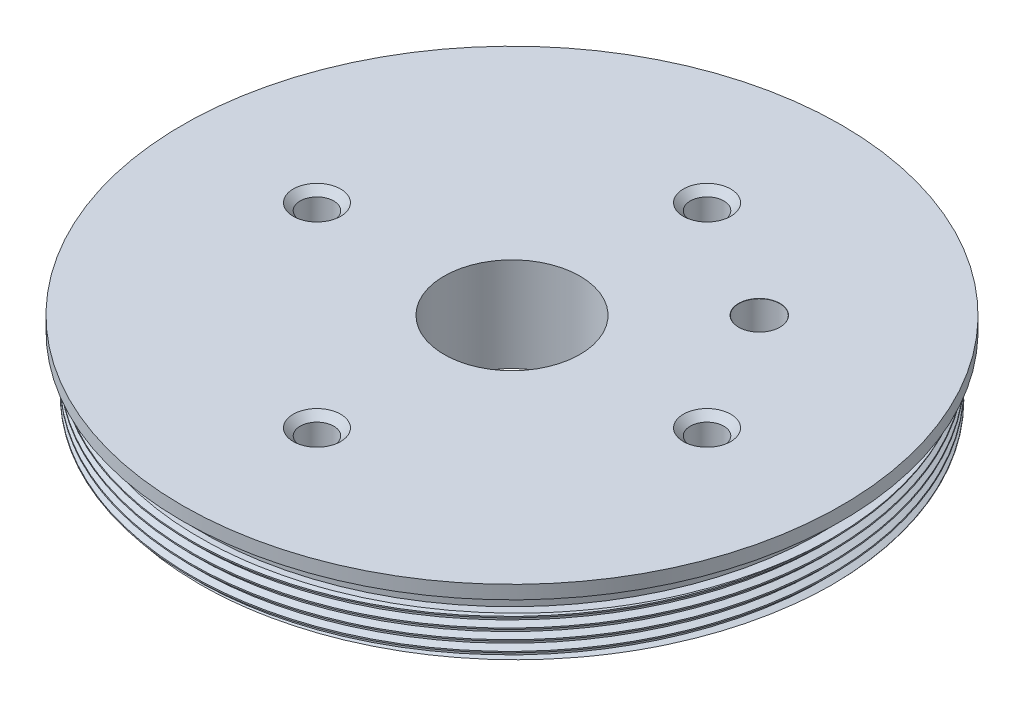
SolidWorks part; units mm, degrees
material "1.4305 (X8CrNiS18-9)"
ref_plane "Ebene vorne" through (0, 0, 0) normal (0, 0, 1) x (1, 0, 0)
ref_plane "Ebene oben" through (0, 0, 0) normal (0, 1, 0) x (1, 0, 0)
ref_plane "Ebene rechts" through (0, 0, 0) normal (1, 0, 0) x (0, 0, -1)
sketch "Sketch1" plane through (0, 0, 0) normal (0, 0, 1) x (1, 0, 0)
  line L0 (0, 0) -> (0, 18.3758) construction
  line L1 (-10.1, 14) -> (-10.1, 0)
  line L2 (-10.1, 0) -> (-47.5, 0)
  line L3 (-47.5, 0) -> (-47.5, 9)
  line L4 (-47.5, 9) -> (-46, 9)
  line L5 (-46, 9) -> (-46, 12)
  line L6 (-46, 12) -> (-49, 12)
  line L10 (-49, 14) -> (-10.1, 14)
  line L19 (-49, 14) -> (-49, 12)
  dimension "D1" = 20.2
  dimension "D2" = 95
  dimension "D3" = 3
  dimension "D4" = 9
  dimension "D5" = 2
  dimension "D6" = 49
  dimension "D11" = 1.5
revolve "Revolve1" add sketch "Sketch1" angle 360 about L0
thread "Thread2" pitch 1.5 method cut profile "Thread Profile2" start angle 0, offset 0, length 0, pitch 1.5, diameter 95
ref_plane "Plane2" through (47.5, 0, 0) normal (0, 0, 1) x (1, 0, 0)
sketch "Thread Profile2" plane through (47.5, 0, 0) normal (0, 0, 1) x (1, 0, 0)
  line L0 (0, 0) -> (0, 1.5) construction
  line L11 (0, 0) -> (0, 1.3125)
  line L12 (0, 1.3125) -> (-0.8119, 0.8437)
  line L13 (-0.8119, 0.8437) -> (-0.8119, 0.4687)
  line L15 (-0.8119, 0.4687) -> (0, 0)
  line L17 (-0.8119, 0.6562) -> (0, 0.6562) construction
  point P2 (0, 0)
  dimension "Pitch" = 1.5
  dimension "Profile_Angle" = 60
  dimension "Profile_Land" = 0.375
  dimension "Profile_Height" = 0.8119
hole_wizard "M6 Tapped Hole1" positions "Sketch31" profile "Sketch32" tap size "M6" standard "DIN"
sketch "Sketch31" plane through (0, 14, 0) normal (0, 1, 0) x (1, 0, 0)
  point P0 (29, 0)
  dimension "D1" = 29
sketch "Sketch32" plane through (29, 14, 0) normal (1, 0, 0) x (0, 0, 1)
  line L0 (0, 0) -> (0, 9.5022)
  line L1 (0, 9.5022) -> (2.5, 8)
  line L2 (2.5, 8) -> (2.5, 1.025)
  line L3 (2.5, 1.025) -> (3.525, 0)
  line L5 (3.525, 0) -> (0, 0)
  line L6 (-2.5, 1.025) -> (-3.525, 0) construction
  line L10 (0, 9.5022) -> (-2.5, 8) construction
  line L11 (0, -6.35) -> (0, 107.95) construction
  dimension "Tap Drill Dia." = 5
  dimension "Tap Drill Depth" = 8
  dimension "Near C'Sink Dia." = 7.05
  dimension "Near C'Sink Angle" = 90
  dimension "Drill Angle" = 118
cosmetic thread "Hole Thread1" parameters "D1"=6, "D2"=6
pattern_circular "CirPattern1" count 4 over 360 about axis through (0, 0, 0) along (0, -1, 0) of "M6 Tapped Hole1" reverse direction yes
cosmetic thread "Hole Thread2" parameters "D1"=6, "D2"=6
cosmetic thread "Hole Thread3" parameters "D1"=6, "D2"=6
cosmetic thread "Hole Thread4" parameters "D1"=6, "D2"=6
hole_wizard "Ø6.1 (6.1) Diameter Hole1" positions "Sketch34" profile "Sketch35" hole size "Ø6.1" standard "DIN" end condition up to next
sketch "Sketch34" plane through (0, 14, 0) normal (0, 1, 0) x (1, 0, 0)
  line L0 (0, 0) -> (18.3848, 18.3848) construction
  line L2 (0, 0) -> (20.014, 0) construction
  point P0 (18.3848, 18.3848)
  dimension "D1" = 26
  dimension "D2" = 45
sketch "Sketch35" plane through (18.3848, 14, -18.3848) normal (1, 0, 0) x (0, 0, 1)
  line L0 (0, 0) -> (0, 14)
  line L1 (0, 14) -> (3.05, 14)
  line L2 (3.05, 14) -> (3.05, 0.025)
  line L3 (3.05, 0.025) -> (3.075, 0)
  line L5 (3.075, 0) -> (0, 0)
  line L6 (-3.05, 0.025) -> (-3.075, 0) construction
  line L11 (0, -6.35) -> (0, 107.95) construction
  dimension "Thru Hole Dia." = 6.1
  dimension "Thru Hole Depth" = 14
  dimension "Near C'Sink Dia." = 6.15
  dimension "Near C'Sink Angle" = 90
sketch "Sketch36" plane through (0, 14, 0) normal (0, 1, 0) x (1, 0, 0)
  circle A0 centre (0, 0) radius 40
  circle A1 centre (0, 0) radius 46 construction
  circle A2 centre (0, 0) radius 34
  dimension "D1" = 6
  dimension "D2" = 6
sketch "Sketch37" plane through (0, 0, 0) normal (0, -1, 0) x (1, 0, 0)
  circle A0 centre (0, 0) radius 42.86
  circle A1 centre (0, 0) radius 75.4953
  dimension "D1" = 85.72
extrude "Cut-Extrude3" cut sketch "Sketch37" against normal blind 3 contours A0 | A1
